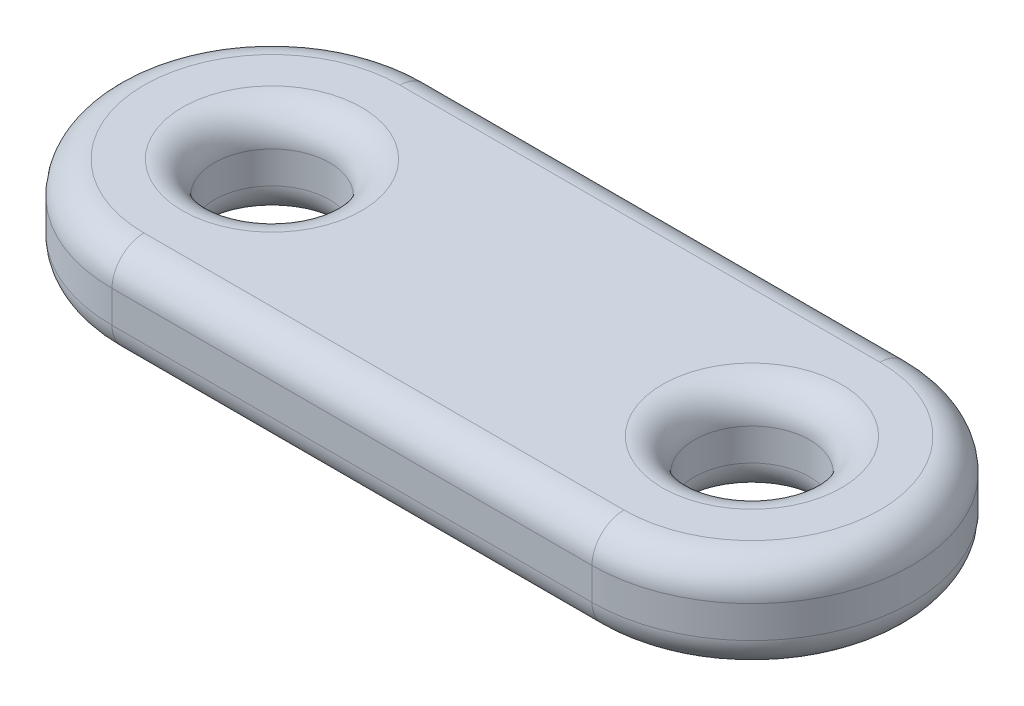
SolidWorks part; units mm, degrees
ref_plane "Front Plane" through (0, 0, 0) normal (0, 0, 1) x (1, 0, 0)
ref_plane "Top Plane" through (0, 0, 0) normal (0, 1, 0) x (1, 0, 0)
ref_plane "Right Plane" through (0, 0, 0) normal (1, 0, 0) x (0, 0, -1)
sketch "Sketch1" plane through (0, 0, 0) normal (0, 1, 0) x (1, 0, 0)
  line L0 (-7.5, 0) -> (7.5, 0) construction
  line L1 (-7.5, 5) -> (7.5, 5)
  line L2 (-7.5, -5) -> (7.5, -5)
  arc A0 (-7.5, 5) -> (-7.5, -5) centre (-7.5, 0) ccw
  arc A1 (7.5, -5) -> (7.5, 5) centre (7.5, 0) ccw
  point P3 (0, 0)
  dimension "D1" = 15
  dimension "D2" = 10
extrude "Boss-Extrude1" add sketch "Sketch1" along normal blind 3
hole_wizard "M3 Clearance Hole1" positions "Sketch2" profile "Sketch3" hole size "M3" standard "ANSI Metric" end condition through all
sketch "Sketch2" plane through (0, 0, 0) normal (0, 1, 0) x (1, 0, 0)
  point P0 (-7.5, 0)
  point P3 (7.5, 0)
sketch "Sketch3" plane through (-7.5, 0, 0) normal (1, 0, 0) x (0, 0, -1)
  line L0 (0, 0) -> (0, 3)
  line L1 (0, 3) -> (1.8, 3)
  line L2 (1.8, 3) -> (1.8, 0)
  line L5 (1.8, 0) -> (0, 0)
  line L11 (0, -6.35) -> (0, 107.95) construction
  dimension "Thru Hole Dia." = 3.6
  dimension "Thru Hole Depth" = 3
fillet "Fillet1" radius 1 12 edges at (0, 0, 5) (12.5, 0, 0) (0, 0, -5) (-12.5, 0, 0) (0, 3, -5) (12.5, 3, 0) (0, 3, 5) (-12.5, 3, 0) (7.5, 0, -1.8) (-7.5, 0, -1.8) (7.5, 3, -1.8) (-7.5, 3, -1.8)
